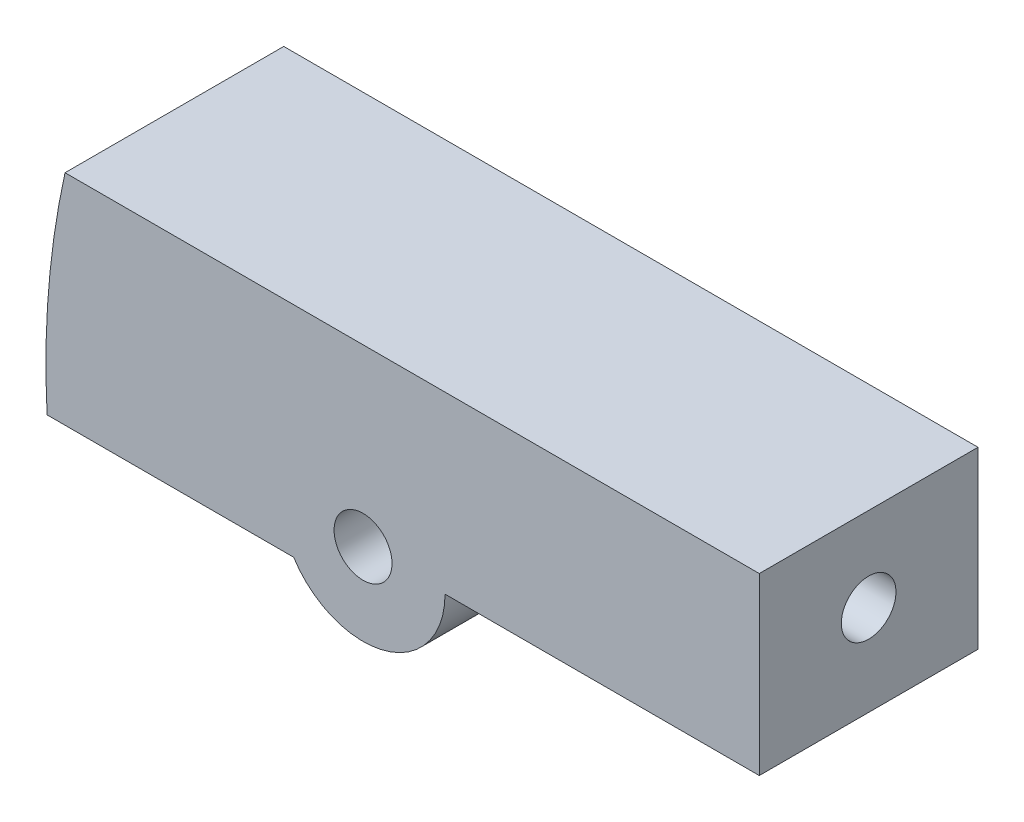
SolidWorks part; units mm, degrees
ref_plane "Front Plane" through (0, 0, 0) normal (0, 0, 1) x (1, 0, 0)
ref_plane "Top Plane" through (0, 0, 0) normal (0, 1, 0) x (1, 0, 0)
ref_plane "Right Plane" through (0, 0, 0) normal (1, 0, 0) x (0, 0, -1)
sketch "Sketch1" plane through (0, 0, 0) normal (0, 0, 1) x (1, 0, 0)
  line L1 (-65, 21) -> (65, 21) construction
  line L2 (-65, 21) -> (-65, 16) construction
  line L3 (-65, 16) -> (65, 16) construction
  line L4 (65, 21) -> (65, 16) construction
  circle A0 centre (0, 0) radius 76.2 construction
  circle A1 centre (0, 0) radius 4 construction
  circle A2 centre (-45, 0) radius 2.5 construction
  circle A3 centre (45, 0) radius 2.5 construction
  dimension "D1" = 152.4
  dimension "D6" = 8
  dimension "D7" = 5
  dimension "D8" = 5
  dimension "D2" = 130
  dimension "D3" = 5
  dimension "D4" = 65
  dimension "D5" = 21
  dimension "D9" = 45
  dimension "D10" = 45
sketch "Sketch2" plane through (0, 0, 0) normal (0, 0, 1) x (1, 0, 0)
  line L0 (-75.5942, -4) -> (-25.764, -4)
  line L1 (-5.764, 16) -> (-5.764, -4)
  line L2 (-65, 16) -> (65, 16) construction
  line L3 (-5.764, 16) -> (-73.9898, 16)
  line L4 (-37.5, 0) -> (-21.764, 0)
  line L5 (-5.764, -4) -> (-25.764, -4)
  line L6 (-21.764, 0) -> (-5.764, 0)
  circle A1 centre (-45, 0) radius 2.65
  circle A2 centre (0, 0) radius 75.7
  circle A3 centre (0, 0) radius 75.7
  circle A4 centre (-45, 0) radius 7.5
  dimension "D2" = 5.3
  dimension "D3" = 15
  dimension "D4" = 20
  dimension "D5" = 20
  dimension "D1" = 0.5
extrude "Boss-Extrude1" add sketch "Sketch2" along normal mid plane 20 contours A4 L0 L3 A3 | L0 A4 A1 | L0 A4 region at (-42.0681, 7.5038, 0) region at (-47.0293, 7.0237, 0) region at (-45, -5.4324, 0)
sketch "Sketch3" plane through (0, 0, 0) normal (0, 0, 1) x (1, 0, 0)
  line L0 (-75.2436, 8.3) -> (-55.2761, 8.3)
  line L1 (-70.2436, 13.3) -> (-76.2436, 16.3)
  line L2 (-55.2761, 8.3) -> (-76.2436, 8.3)
  line L4 (-49.2436, 13.3) -> (-76.2436, 13.3)
  line L5 (-76.2436, 8.3) -> (-76.2436, 13.3)
  line L6 (-76.2436, 16.3) -> (-76.2436, 13.3)
  line L7 (-5.764, 16) -> (-73.9898, 16) construction
  line L8 (-48.2436, 12.3) -> (-25.2436, 12.3)
  line L9 (-25.2436, 12.3) -> (-23.7436, 10.8)
  line L10 (-49.2436, 13.3) -> (-48.2436, 12.3)
  line L11 (-23.7436, 10.8) -> (11.2564, 10.8)
  line L12 (-55.2761, 8.3) -> (11.2564, 8.3)
  line L13 (11.2564, 8.3) -> (11.2564, 10.8)
  arc A1 (-73.9898, 16) -> (-75.5942, -4) centre (0, 0) ccw construction
  dimension "D1" = 5
  dimension "D2" = 27
  dimension "D3" = 3
  dimension "D4" = 1
  dimension "D5" = 5
  dimension "D6" = 7.7
  dimension "D7" = 23
  dimension "D8" = 1
  dimension "D9" = 45
  dimension "D10" = 45
  dimension "D11" = 35
  dimension "D12" = 1.5
revolve "Cut-Revolve1" cut sketch "Sketch3" angle 360 about L0 region at (-39.3245, 10.3042, 0) region at (-74.2436, 14.3, 0)
sketch "Sketch4" plane through (0, 0, -10) normal (0, 0, -1) x (-1, 0, 0)
  circle A1 centre (0, 0) radius 75.7 construction
  circle A2 centre (0, 0) radius 75.7
  circle A3 centre (0, 0) radius 74
  point P0 (0, 0)
  dimension "D1" = 148
extrude "Cut-Extrude5" cut sketch "Sketch4" against normal through all
sketch "Sketch5" plane through (0, 0, -10) normal (0, 0, -1) x (-1, 0, 0)
  line L0 (5.764, 16) -> (72.2496, 16) construction
  line L1 (5.764, 0) -> (8.764, 0)
  line L2 (5.764, 0) -> (5.764, 16)
  line L3 (5.764, 16) -> (8.764, 16)
  line L4 (8.764, 0) -> (8.764, 16)
  dimension "D1" = 3
extrude "Cut-Extrude6" cut sketch "Sketch5" against normal through all
